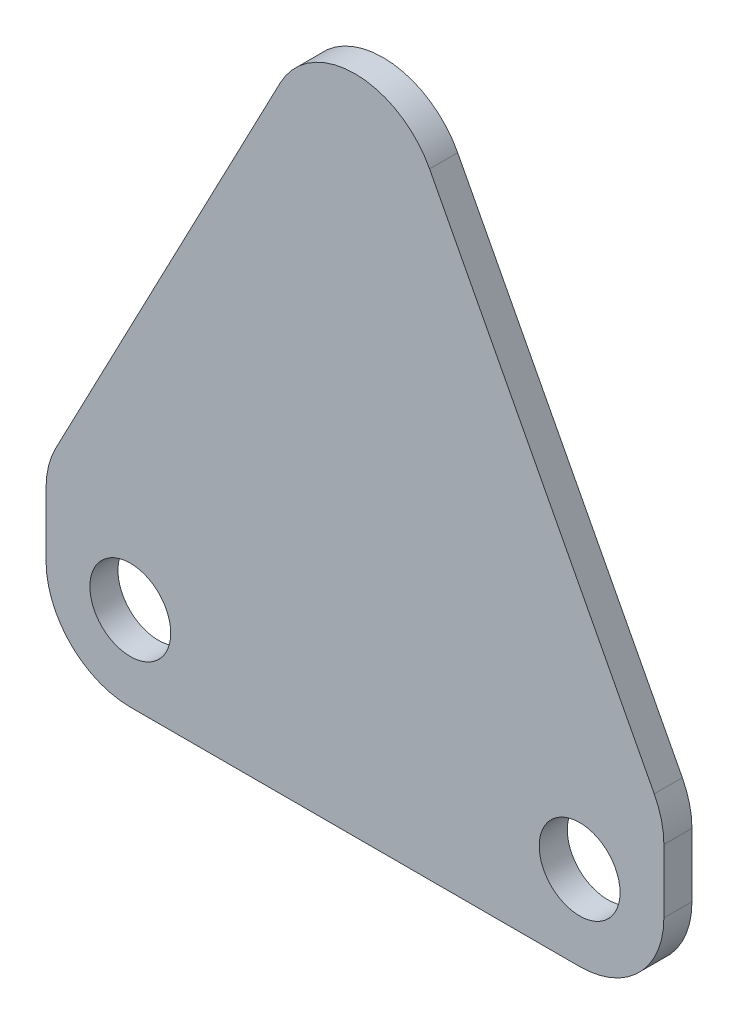
SolidWorks part; units mm, degrees
ref_plane "Front Plane" through (0, 0, 0) normal (0, 0, 1) x (1, 0, 0)
ref_plane "Top Plane" through (0, 0, 0) normal (0, 1, 0) x (1, 0, 0)
ref_plane "Right Plane" through (0, 0, 0) normal (1, 0, 0) x (0, 0, -1)
sketch "Sketch1" plane through (0, 0, 0) normal (0, 0, 1) x (1, 0, 0)
  line L0 (-17.4625, 0) -> (17.4625, 0)
  line L1 (17.4625, 0) -> (17.4625, 9.525)
  line L2 (17.4625, 9.525) -> (0, 42.8625)
  line L3 (0, 42.8625) -> (-17.4625, 9.525)
  line L4 (-17.4625, 9.525) -> (-17.4625, 0)
  line L5 (-12.7, 4.7625) -> (12.7, 4.7625) construction
  circle A0 centre (-12.7, 4.7625) radius 2.286
  circle A1 centre (12.7, 4.7625) radius 2.286
  point P4 (0, 0)
  point P12 (0, 4.7625)
  point P13 (0, 0)
  dimension "D3" = 4.572
  dimension "D1" = 25.4
  dimension "D2" = 9.525
  dimension "D4" = 4.7625
  dimension "D5" = 4.7625
  dimension "D7" = 38.1
extrude "Boss-Extrude1" add sketch "Sketch1" along normal blind 1.5875
fillet "Fillet1" radius 4.7625 5 edges at (-17.4625, 0, 0.7937) (-17.4625, 9.525, 0.7937) (17.4625, 0, 0.7937) (0, 42.8625, 0.7937) (17.4625, 9.525, 0.7937)
ref_axis "Axis1" through (17.4625, 4.7625, 0) along (-1, 0, 0)
